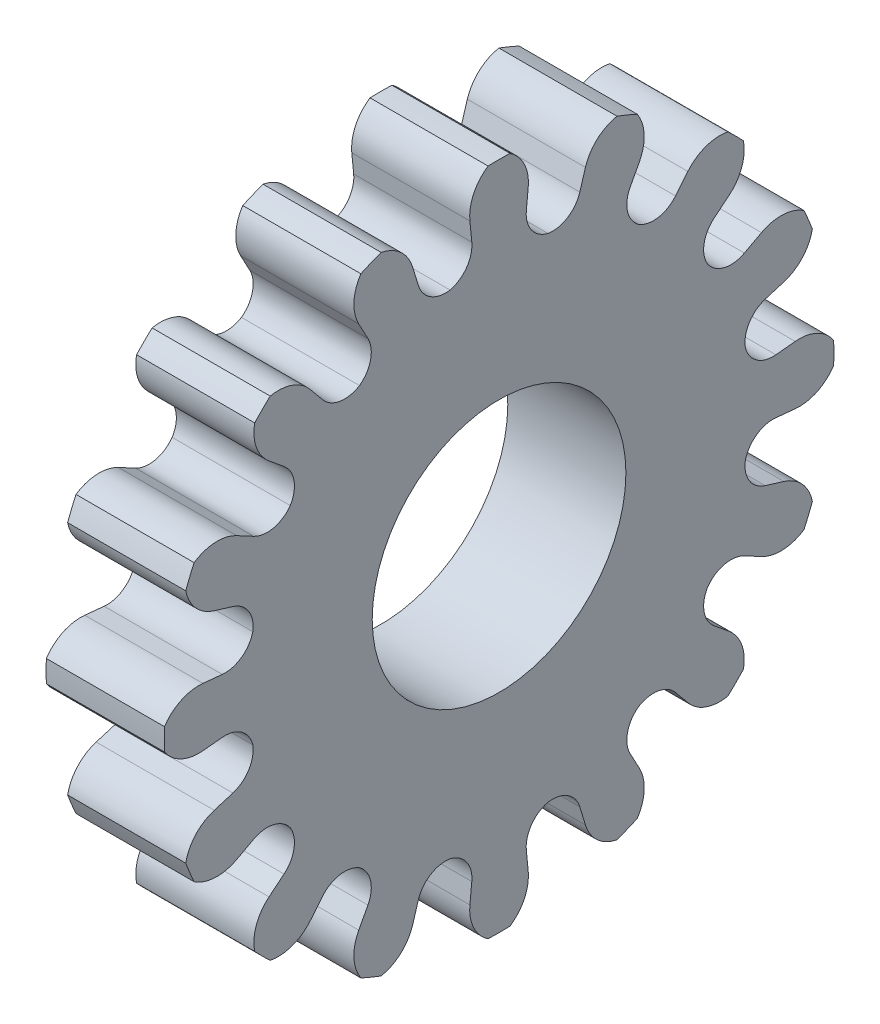
SolidWorks part; units mm, degrees
material "Acrylic (Medium-high impact)"
ref_plane "Front Plane" through (0, 0, 0) normal (0, 0, 1) x (1, 0, 0)
ref_plane "Top Plane" through (0, 0, 0) normal (0, 1, 0) x (1, 0, 0)
ref_plane "Right Plane" through (0, 0, 0) normal (1, 0, 0) x (0, 0, -1)
sketch "Sketch1" plane through (0, 0, 0) normal (1, 0, 0) x (0, 0, -1)
  line L0 (0, 0) -> (26.5454, 0) construction
  line L1 (0, 0) -> (7.8279, 1.5571) construction
  line L2 (0, 0) -> (23.6724, 2.3315) construction
  line L3 (0, 0) -> (24.1888, 0.7919) construction
  line L4 (6.7175, 0.6616) -> (7.9615, 0.7841)
  line L5 (0, 0) -> (6.6203, 1.3169)
  line L6 (6.7175, -0.6616) -> (7.9615, -0.7841)
  line L7 (0, 0) -> (6.6203, -1.3169)
  circle A0 centre (0, 0) radius 6.75 construction
  circle A1 centre (0, 0) radius 8 construction
  circle A2 centre (0, 0) radius 9 construction
  arc A3 (8.9952, 0.2945) -> (7.9615, 0.7841) centre (8.0704, -0.3218) ccw
  arc A4 (6.6203, 1.3169) -> (6.7175, 0.6616) centre (0, 0) cw
  arc A5 (8.9952, 0.2945) -> (8.9952, -0.2945) centre (0, 0) cw
  arc A6 (8.9952, -0.2945) -> (7.9615, -0.7841) centre (8.0704, 0.3218) cw
  arc A7 (6.6203, -1.3169) -> (6.7175, -0.6616) centre (0, 0) ccw
  point P210 (0, 0)
  dimension "D1" = 13.5
  dimension "D2" = 16
  dimension "D3" = 18
  dimension "D4" = 11.25
  dimension "D5" = 5.625
  dimension "D6" = 1.875
extrude "Boss-Extrude2" add sketch "Sketch1" along normal blind 3.175
fillet "Fillet1" radius 0.7675 2 edges at (1.5875, 0.6616, -6.7175) (1.5875, -0.6616, -6.7175)
pattern_circular "CirPattern1" count 16 over 360 about axis through (3.175, 0, 0) along (-1, 0, 0) reverse direction yes of bodies 102
sketch "Sketch2" plane through (3.175, 0, 0) normal (1, 0, 0) x (0, 0, -1)
  circle A0 centre (0, 0) radius 3.41
  point P5 (0, 0)
  dimension "D1" = 6.82
extrude "Cut-Extrude1" cut sketch "Sketch2" against normal through all contours A0
sketch "Sketch4" [suppressed] plane through (3, 0, 0) normal (1, 0, 0) x (0, 0, -1)
  line L2 (8.221, 2) -> (8.221, -2)
  line L3 (8.221, 2) -> (9.5, 2)
  line L4 (8.221, -2) -> (9.5, -2)
  line L5 (9.5, 2) -> (9.5, -2)
  circle A0 centre (8.221, 0) radius 2
  arc A2 (9.4949, -0.3108) -> (9.4949, 0.3108) centre (0, 0) ccw construction
  dimension "D2" = 4
  dimension "D1" = 8.221
combine bodies "Combine1" operation type add bodies to combine 151 139 152 140 153 141 138 142 143 144 145 146 147 148 149 150
equation "\"bd\"= \"pd\" * cos ( \"alpha\" )'base diameter"
equation "\"m\"= 1.0'module"
equation "\"alpha\"= 20deg'pressure angle"
equation "\"z\"= 16'number of teeth"
equation "\"D2@Sketch1\"=\"pd\""
equation "\"od\"= \"pd\" + 2 * \"m\"'outer/tip diameter"
equation "\"D4@Sketch1\"= 180deg / \"z\""
equation "\"pd\"= \"m\" * \"z\"'pitch/reference diameter"
equation "\"D1@CirPattern1\"=\"z\""
equation "\"rd\"= \"pd\" - 2.5 * \"m\"'root diameter"
equation "\"D1@Sketch1\"=\"rd\""
equation "\"D3@Sketch1\"=\"od\""
equation "\"D1@Fillet1\"=(\"bd\"-\"rd\")/2"
equation "\"D5@Sketch1\"=90/\"z\""
